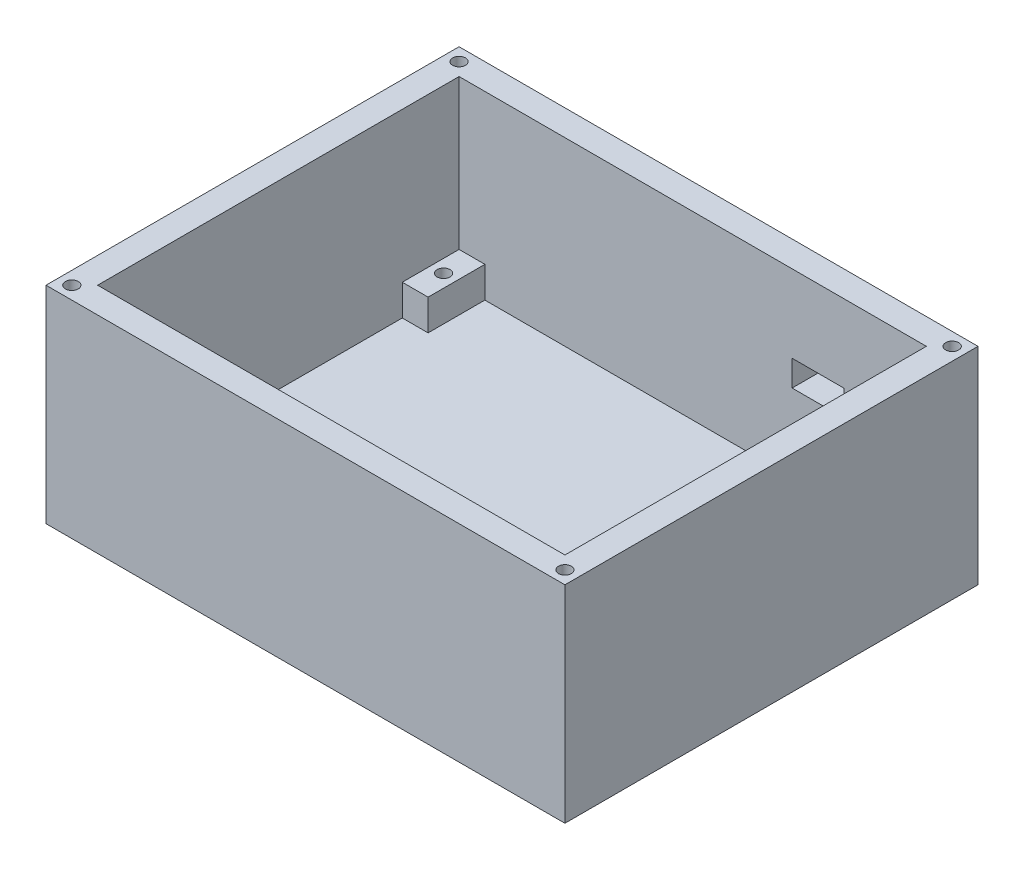
SolidWorks part; units mm, degrees
ref_plane "Plano frontal" through (0, 0, 0) normal (0, 0, 1) x (1, 0, 0)
ref_plane "Plano superior" through (0, 0, 0) normal (0, 1, 0) x (1, 0, 0)
ref_plane "Plano direito" through (0, 0, 0) normal (1, 0, 0) x (0, 0, -1)
sketch "Sketch1" plane through (0, 0, 0) normal (0, 1, 0) x (1, 0, 0)
  line L1 (-50.25, -40) -> (50.25, -40)
  line L2 (-50.25, -40) -> (-50.25, 40)
  line L3 (-50.25, 40) -> (50.25, 40)
  line L4 (50.25, -40) -> (50.25, 40)
  line L5 (-50.25, -40) -> (50.25, 40) construction
  line L6 (-50.25, 40) -> (50.25, -40) construction
  point P0 (0, 0)
  dimension "D1" = 80
  dimension "D2" = 100.5
extrude "Boss-Extrude1" add sketch "Sketch1" along normal blind 40
sketch "Sketch2" plane through (0, 40, 0) normal (0, 1, 0) x (1, 0, 0)
  line L0 (50.25, -40) -> (50.25, 40) construction
  line L1 (-45.25, -35) -> (45.25, -35)
  line L2 (-45.25, -35) -> (-45.25, 35)
  line L3 (-45.25, 35) -> (45.25, 35)
  line L4 (45.25, -35) -> (45.25, 35)
  line L5 (-45.25, -35) -> (45.25, 35) construction
  line L6 (-45.25, 35) -> (45.25, -35) construction
  line L7 (50.25, 40) -> (-50.25, 40) construction
  point P0 (0, 0)
  dimension "D1" = 5
  dimension "D2" = 5
extrude "Cut-Extrude1" cut sketch "Sketch2" against normal blind 35
sketch "Sketch3" plane through (0, 5, 0) normal (0, 1, 0) x (1, 0, 0)
  line L1 (45.25, 35) -> (36.25, 35)
  line L2 (45.25, 35) -> (45.25, 24)
  line L3 (45.25, 24) -> (36.25, 24)
  line L4 (36.25, 35) -> (36.25, 24)
  line L5 (45.25, -35) -> (36.25, -35)
  line L6 (45.25, -35) -> (45.25, -24)
  line L7 (45.25, -24) -> (36.25, -24)
  line L8 (36.25, -35) -> (36.25, -24)
  line L9 (-45.25, -35) -> (-40.25, -35)
  line L10 (-45.25, -35) -> (-45.25, -24)
  line L11 (-45.25, -24) -> (-40.25, -24)
  line L12 (-40.25, -35) -> (-40.25, -24)
  line L13 (-45.25, 35) -> (-40.25, 35)
  line L14 (-45.25, 35) -> (-45.25, 24)
  line L15 (-45.25, 24) -> (-40.25, 24)
  line L16 (-40.25, 35) -> (-40.25, 24)
  dimension "D1" = 11
  dimension "D2" = 9
  dimension "D3" = 5
extrude "Boss-Extrude2" add sketch "Sketch3" along normal blind 6
sketch "Sketch4" plane through (0, 11, 0) normal (0, 1, 0) x (1, 0, 0)
  line L0 (36.25, 24) -> (45.25, 24) construction
  line L1 (36.25, 35) -> (36.25, 24) construction
  line L2 (45.25, -24) -> (36.25, -24) construction
  line L3 (36.25, -24) -> (36.25, -35) construction
  line L4 (-40.25, -24) -> (-45.25, -24) construction
  line L5 (-40.25, -35) -> (-40.25, -24) construction
  line L6 (-40.25, 24) -> (-40.25, 35) construction
  line L7 (-45.25, 24) -> (-40.25, 24) construction
  circle A1 centre (-42.75, -29.5) radius 1.25
  circle A2 centre (40.75, -29.5) radius 1.25
  circle A3 centre (40.75, 29.5) radius 1.25
  circle A4 centre (-42.75, 29.5) radius 1.25
  point P14 (40.75, 24)
  point P17 (36.25, 29.5)
  point P20 (40.75, -24)
  point P23 (36.25, -29.5)
  point P27 (-42.75, -24)
  point P30 (-40.25, -29.5)
  point P34 (-40.25, 29.5)
  point P37 (-42.75, 24)
  dimension "D1" = 2.5
extrude "Cut-Extrude2" cut sketch "Sketch4" against normal blind 6
sketch "Sketch5" plane through (0, 0, -40) normal (0, 0, -1) x (-1, 0, 0)
  line L0 (-29.25, 0) -> (-29.25, 40) construction
  line L1 (-50.25, 0) -> (50.25, 0) construction
  line L2 (-50.25, 40) -> (50.25, 40) construction
  line L3 (-50.25, 40) -> (-50.25, 0) construction
  line L4 (-50.25, 20) -> (50.25, 20) construction
  line L5 (50.25, 40) -> (50.25, 0) construction
  line L7 (-29.25, 20) -> (-19.25, 20)
  line L8 (-29.25, 20) -> (-29.25, 25)
  line L9 (-29.25, 25) -> (-19.25, 25)
  line L10 (-19.25, 20) -> (-19.25, 25)
  dimension "D1" = 21
  dimension "D2" = 20
  dimension "D3" = 10
  dimension "D4" = 5
extrude "Cut-Extrude3" cut sketch "Sketch5" against normal up to next and the other way through all
sketch "Sketch6" plane through (0, 40, 0) normal (0, 1, 0) x (1, 0, 0)
  circle A0 centre (-47.75, 37.5) radius 1.25
  circle A1 centre (-47.75, -37.5) radius 1.25
  circle A2 centre (47.75, -37.5) radius 1.25
  circle A3 centre (47.75, 37.5) radius 1.25
  point P12 (0, 0)
  point P13 (0, 0)
  point P14 (0, 0)
  point P15 (0, 0)
  dimension "D1" = 2.5
extrude "Cut-Extrude4" cut sketch "Sketch6" against normal blind 10
